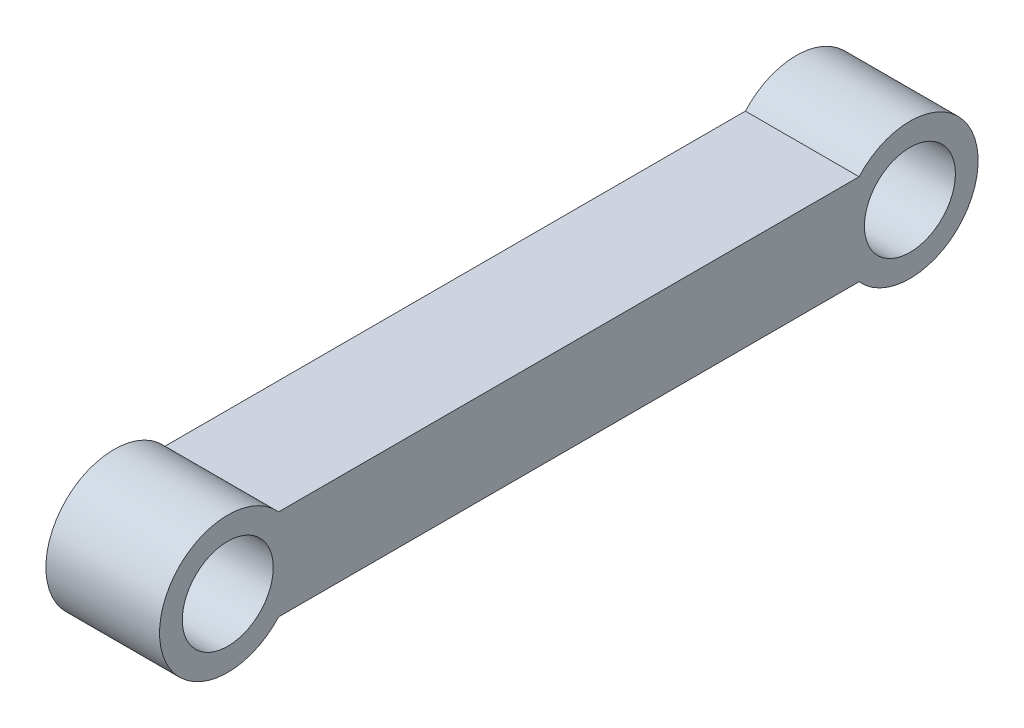
SolidWorks part; units mm, degrees
material "Thornel Mat VMA"
ref_plane "Front Plane" through (0, 0, 0) normal (0, 0, 1) x (1, 0, 0)
ref_plane "Top Plane" through (0, 0, 0) normal (0, 1, 0) x (1, 0, 0)
ref_plane "Right Plane" through (0, 0, 0) normal (1, 0, 0) x (0, 0, -1)
sketch "LinkFrame" plane through (0, 0, 0) normal (1, 0, 0) x (0, 0, -1)
  line L0 (-340.3455, -226.2633) -> (259.6545, -226.2633) construction
  line L1 (-295.6242, -186.2633) -> (214.9331, -186.2633)
  line L2 (-295.6242, -266.2633) -> (214.9331, -266.2633)
  arc A1 (214.9331, -266.2633) -> (214.9331, -186.2633) centre (259.6545, -226.2633) ccw
  arc A2 (-295.6242, -186.2633) -> (-295.6242, -266.2633) centre (-340.3455, -226.2633) ccw
  circle A5 centre (-340.3455, -226.2633) radius 40
  circle A6 centre (259.6545, -226.2633) radius 40
  dimension "D1" = 120
  dimension "D2" = 120
  dimension "D5" = 80
  dimension "D6" = 80
  dimension "D3" = 600
  dimension "D4" = 80
  dimension "D7" = 44.7214
  dimension "D8" = 44.7214
extrude "Boss-Extrude1" add sketch "LinkFrame" along normal blind 100
equation "\"D1@LinkFrame\" = 1.5 * \"HoleMountDiameter@PrintingPress.Assembly\""
equation "\"D2@LinkFrame\" = 1.5 * \"HoleMountDiameter@PrintingPress.Assembly\""
equation "\"LinkLength\"= 60cm"
equation "\"D3@LinkFrame\" = \"LinkLength\""
equation "\"D4@LinkFrame\" = \"HoleMountDiameter@PrintingPress.Assembly\""
equation "\"D5@LinkFrame\"=\"HoleMountDiameter@PrintingPress.Assembly\""
equation "\"D6@LinkFrame\"=\"HoleMountDiameter@PrintingPress.Assembly\""
equation "\"D1@Boss-Extrude1\"=\"RivetLength@PrintingPress.Assembly\""
